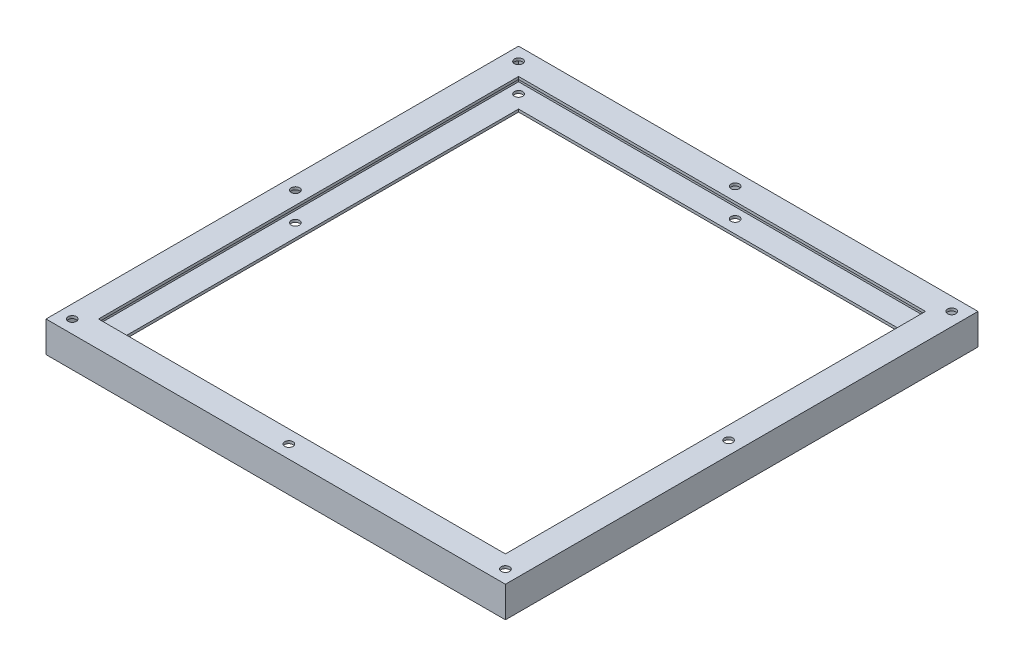
SolidWorks part; units mm, degrees
material "1.4000 (X6Cr13)"
ref_plane "Plan de face" through (0, 0, 0) normal (0, 0, 1) x (1, 0, 0)
ref_plane "Plan de dessus" through (0, 0, 0) normal (0, 1, 0) x (1, 0, 0)
ref_plane "Plan de droite" through (0, 0, 0) normal (1, 0, 0) x (0, 0, -1)
sketch "Esquisse1" plane through (0, 0, 0) normal (0, 1, 0) x (1, 0, 0)
  line L0 (0, 0) -> (350, 0)
  line L1 (350, 0) -> (350, 360)
  line L2 (350, 360) -> (0, 360)
  line L3 (0, 360) -> (0, 0)
  line L4 (20, 360) -> (20, 340) construction
  line L5 (20, 340) -> (330, 340)
  line L6 (330, 340) -> (330, 20)
  line L7 (330, 20) -> (20, 20)
  line L8 (20, 20) -> (20, 340)
  line L9 (40, 340) -> (40, 320) construction
  line L10 (40, 320) -> (310, 320) construction
  line L11 (310, 320) -> (310, 40) construction
  line L12 (310, 40) -> (40, 40) construction
  line L13 (40, 40) -> (40, 320) construction
  line L14 (0, 360) -> (40, 320) construction
  line L15 (350, 360) -> (310, 320) construction
  line L16 (310, 40) -> (350, 0) construction
  line L17 (40, 40) -> (0, 0) construction
  line L18 (310, 260) -> (250, 260) construction
  line L19 (250, 260) -> (250, 320) construction
  line L20 (2, 358) -> (348, 358)
  line L21 (348, 358) -> (348, 2)
  line L22 (348, 2) -> (2, 2)
  line L23 (2, 2) -> (2, 358)
  line L24 (340, 350) -> (10, 350) construction
  line L25 (10, 10) -> (340, 10) construction
  line L26 (340, 350) -> (340, 10) construction
  line L27 (10, 350) -> (10, 10) construction
  line L28 (20, 350) -> (10, 350) construction
  circle A0 centre (10, 10) radius 3.175
  circle A1 centre (175, 10) radius 3.175
  circle A2 centre (340, 10) radius 3.175
  circle A3 centre (340, 180) radius 3.175
  circle A4 centre (10, 180) radius 3.175
  circle A5 centre (340, 350) radius 3.175
  circle A6 centre (175, 350) radius 3.175
  circle A7 centre (10, 350) radius 3.175
  dimension "D16" = 280
  dimension "D1" = 20
  dimension "D2" = 20
  dimension "D3" = 20
  dimension "D4" = 350
  dimension "D5" = 360
  dimension "D6" = 20
  dimension "D7" = 310
  dimension "D8" = 320
  dimension "D9" = 20
  dimension "D10" = 20
  dimension "D11" = 20
  dimension "D12" = 20
  dimension "D13" = 60
  dimension "D14" = 60
  dimension "D15" = 270
  dimension "D17" = 2
extrude "Boss.-Extru.2" add sketch "Esquisse1" along normal blind 23.5 contours L23 L22 L21 L20 L7 L8 L5 L6 | L2 L3 L0 L1 L22 L23 L20 L21 region at (0.5021, 0, -180) region at (175, 0, -357.5036)
extrude "Enlèv. mat.-Extru.1" cut sketch "Esquisse1<4>" along normal blind 19.5 from offset 2 contours L23 L20 L21 L22
sketch "Esquisse1<4>" plane through (0, 0, 0) normal (0, 1, 0) x (1, 0, 0) same geometry as "Esquisse1"
